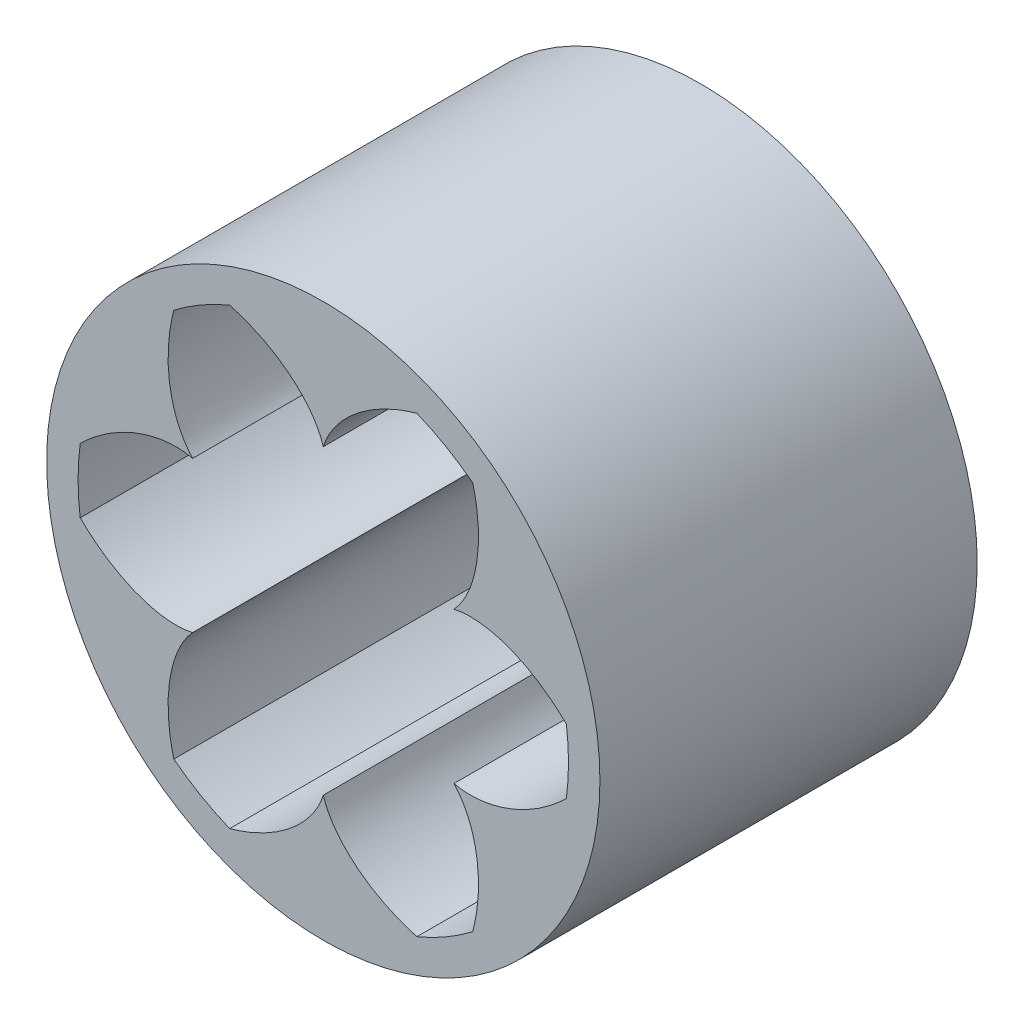
SolidWorks part; units mm, degrees
ref_plane "前视基准面" through (0, 0, 0) normal (0, 0, 1) x (1, 0, 0)
ref_plane "上视基准面" through (0, 0, 0) normal (0, 1, 0) x (1, 0, 0)
ref_plane "右视基准面" through (0, 0, 0) normal (1, 0, 0) x (0, 0, -1)
other "Configuration Table"
sketch "草图1" plane through (0, 0, 0) normal (0, 0, 1) x (1, 0, 0)
  line L0 (0, 0) -> (1.0392, 0.6) construction
  line L1 (0, 0) -> (0.9706, 0.5741)
  line L2 (0, 0) -> (0.9706, -0.5741)
  line L3 (0, 0) -> (1.0392, -0.6) construction
  line L4 (0, 0) -> (1.95, 0) construction
  line L5 (1.0392, 0.6) -> (1.0392, -0.6) construction
  circle A0 centre (0, 0) radius 1.05
  circle A1 centre (0, 0) radius 1.95
  circle A2 centre (0, 0) radius 1.1276 construction
  circle A3 centre (0, 0) radius 1.2 construction
  circle A4 centre (0, 0) radius 2.2
  spline S0 degree 4 poles (0.9706, 0.5741) (0.978, 0.5784) (0.9995, 0.5891) (1.0435, 0.6029) (1.1173, 0.6152) (1.2143, 0.6162) (1.3378, 0.5998) (1.4781, 0.559) (1.6242, 0.4926) (1.7702, 0.4) (1.9035, 0.2902) (2.0236, 0.166) (2.1352, 0.0233) (2.2543, -0.1669) (2.3663, -0.4104) (2.4536, -0.7095) (2.4985, -1.0525) (2.493, -1.3986) (2.4419, -1.74) (2.3458, -2.0731) (2.2132, -2.3902) (2.0397, -2.6928) (1.8421, -2.9689) (1.6015, -3.2316) (1.4036, -3.4131) (1.1635, -3.5957) (1.0197, -3.6904) (0.8529, -3.7933) (0.7575, -3.8405) (0.6798, -3.8826) (0.656, -3.8928) (0.639, -3.9012) knots 0 0 0 0 0 0.005604 0.015718 0.02996 0.048734 0.068727 0.096889 0.125051 0.153212 0.181374 0.209535 0.237696 0.271429 0.327752 0.384075 0.440398 0.496721 0.553044 0.609367 0.66569 0.722013 0.778336 0.834659 0.890982 0.909091 0.954545 0.977273 0.988636 1 1 1 1 1 construction
  spline S1 degree 4 poles (0.9706, 0.5741) (0.978, 0.5784) (0.9995, 0.5891) (1.0435, 0.6029) (1.1173, 0.6152) (1.2143, 0.6162) (1.3378, 0.5998) (1.4781, 0.559) (1.6242, 0.4926) (1.7702, 0.4) (1.9035, 0.2902) (2.0236, 0.166) (2.1352, 0.0233) (2.2543, -0.1669) (2.3663, -0.4104) (2.4536, -0.7095) (2.4985, -1.0525) (2.493, -1.3986) (2.4419, -1.74) (2.3458, -2.0731) (2.2132, -2.3902) (2.0397, -2.6928) (1.8421, -2.9689) (1.6015, -3.2316) (1.4036, -3.4131) (1.2254, -3.5486) (1.1404, -3.6085) (1.1196, -3.6228) knots 0 0 0 0 0 0.005604 0.015718 0.02996 0.048734 0.068727 0.096889 0.125051 0.153212 0.181374 0.209535 0.237696 0.271429 0.327752 0.384075 0.440398 0.496721 0.553044 0.609367 0.66569 0.722013 0.778336 0.834659 0.890982 0.909091 0.909091 0.909091 0.909091 0.909091
  spline S2 degree 4 poles (0.9706, -0.5741) (0.978, -0.5784) (0.9995, -0.5891) (1.0435, -0.6029) (1.1173, -0.6152) (1.2143, -0.6162) (1.3378, -0.5998) (1.4781, -0.559) (1.6242, -0.4926) (1.7702, -0.4) (1.9035, -0.2902) (2.0236, -0.166) (2.1352, -0.0233) (2.2543, 0.1669) (2.3663, 0.4104) (2.4536, 0.7095) (2.4985, 1.0525) (2.493, 1.3986) (2.4419, 1.74) (2.3458, 2.0731) (2.2132, 2.3902) (2.0397, 2.6928) (1.8421, 2.9689) (1.6015, 3.2316) (1.4036, 3.4131) (1.1635, 3.5957) (1.0197, 3.6904) (0.8529, 3.7933) (0.7575, 3.8405) (0.6798, 3.8826) (0.656, 3.8928) (0.639, 3.9012) knots 0 0 0 0 0 0.005604 0.015718 0.02996 0.048734 0.068727 0.096889 0.125051 0.153212 0.181374 0.209535 0.237696 0.271429 0.327752 0.384075 0.440398 0.496721 0.553044 0.609367 0.66569 0.722013 0.778336 0.834659 0.890982 0.909091 0.954545 0.977273 0.988636 1 1 1 1 1 construction
  spline S3 degree 4 poles (0.9706, -0.5741) (0.978, -0.5784) (0.9995, -0.5891) (1.0435, -0.6029) (1.1173, -0.6152) (1.2143, -0.6162) (1.3378, -0.5998) (1.4781, -0.559) (1.6242, -0.4926) (1.7702, -0.4) (1.9035, -0.2902) (2.0236, -0.166) (2.1352, -0.0233) (2.2543, 0.1669) (2.3663, 0.4104) (2.4536, 0.7095) (2.4985, 1.0525) (2.493, 1.3986) (2.4419, 1.74) (2.3458, 2.0731) (2.2132, 2.3902) (2.0397, 2.6928) (1.8421, 2.9689) (1.6015, 3.2316) (1.4036, 3.4131) (1.2254, 3.5486) (1.1404, 3.6085) (1.1196, 3.6228) knots 0 0 0 0 0 0.005604 0.015718 0.02996 0.048734 0.068727 0.096889 0.125051 0.153212 0.181374 0.209535 0.237696 0.271429 0.327752 0.384075 0.440398 0.496721 0.553044 0.609367 0.66569 0.722013 0.778336 0.834659 0.890982 0.909091 0.909091 0.909091 0.909091 0.909091
  point P16 (1.0392, 0)
  dimension "内啮合齿顶圆直径" = 2.1
  dimension "内啮合分度圆直径" = 2.4
  dimension "内啮合基圆直径" = 2.2553
  dimension "内啮合齿根圆直径" = 3.9
  dimension "外径" = 4.4
  dimension "渐开线镜像线夹角" = 30
extrude "凸台-拉伸1" add sketch "草图1" along normal blind 3 contours A4 | A0
extrude "切除-拉伸2" cut sketch "草图1<3>" along normal through all contours A0 S3 A1 S1 region at (1.4166, 0, 0)
sketch "草图1<3>" plane through (0, 0, 0) normal (0, 0, 1) x (1, 0, 0) same geometry as "草图1"
pattern_circular "阵列(圆周)1" count 6 over 360 about axis through (0, 0, 3) along (0, 0, 1) of "切除-拉伸2"
equation "\"m\"= 0.4'模数"
equation "\"z1\"= 6'外啮合齿轮数"
equation "\"a\"= 20度'压力角"
equation "\"z2\"= 6'内啮合齿轮数"
equation "\"hax\"= 1'齿顶高系数"
equation "\"cx\"= 0.25'顶隙系数"
equation "\"ha\"= \"hax\" * \"m\"'齿顶高"
equation "\"hf\"= ( \"hax\" + \"cx\" ) * \"m\"'齿根高"
equation "\"d1\"= \"m\" * \"z1\"'外啮合分度圆直径"
equation "\"da1\"= ( \"z1\" + 2 ) * \"m\"'外啮合齿顶圆直径"
equation "\"df1\"= \"d1\" - 2 * \"hf\"'外啮合齿根圆直径"
equation "\"db1\"= \"d1\" * cos ( \"a\" )'外啮合基圆直径"
equation "\"p\"= \"m\" * PI'齿距"
equation "\"d2\"= \"m\" * \"z2\"'内啮合分度圆直径"
equation "\"db2\"= \"d2\" * cos ( \"a\" )'内啮合基圆直径"
equation "\"da2\"= ( \"z2\" - 2 ) * \"m\"'内啮合齿顶圆直径"
equation "\"df2\"= \"d2\" + 2 * \"hf\"'内啮合齿根圆直径"
equation "\"内啮合齿顶圆直径@草图1\" = \"da2\" + 1 * \"hf\""
equation "\"内啮合齿根圆直径@草图1\"= \"df2\" + 1 * \"hf\""
equation "\"内啮合分度圆直径@草图1\"= \"d2\""
equation "\"内啮合基圆直径@草图1\"= \"db2\""
equation "\"渐开线镜像线夹角@草图1\"= 360度 / 4 / \"z2\" + 360度 / 4 / \"z2\""
equation "\"do\"= IIF ( \"edo\" >= ( \"df2\" + 1 ) , \"edo\" , ( \"df2\" + 1 ) )'外圈直径"
equation "\"h\"= 3'厚度"
equation "\"外径@草图1\"= \"do\""
equation "\"厚度@凸台-拉伸1\"= \"h\""
equation "\"内啮合齿轮数@阵列(圆周)1\"= \"z2\""
equation "\"edo\"= 3'期望的外圈直径"
equation "\"sss\"= 0.8'松度"
